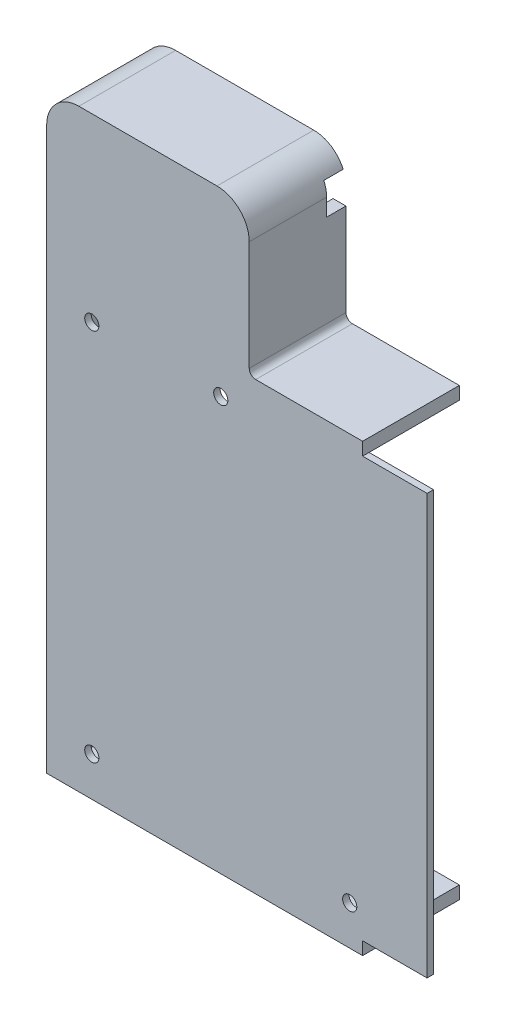
SolidWorks part; units mm, degrees
other "Markup1"
sketch "Sketch13" plane through (0.4487, 1125.5894, 1303.4729) normal (-0.633, 0.4523, -0.6282) x (-0.2198, -0.8831, -0.4145)
ref_plane "Front Plane" through (0, 0, 0) normal (0, 0, 1) x (1, 0, 0)
ref_plane "Top Plane" through (0, 0, 0) normal (0, 1, 0) x (1, 0, 0)
ref_plane "Right Plane" through (0, 0, 0) normal (1, 0, 0) x (0, 0, -1)
sketch "Sketch3" plane through (0, 0, 1303.4729) normal (0, 0, 1) x (1, 0, 0)
  line L0 (787.6501, 933.5894) -> (787.6501, 1120.5894) construction
  line L1 (787.6501, 1035.4965) -> (787.6501, 1120.5894)
  line L3 (818.0661, 1100.5894) -> (834.6501, 1100.5894) construction
  line L4 (815.0661, 1120.5894) -> (815.0661, 1103.5894) construction
  line L5 (790.6501, 1123.5894) -> (812.0661, 1123.5894) construction
  line L7 (818.0661, 1100.5894) -> (834.6501, 1100.5894)
  line L8 (815.0661, 1120.5894) -> (815.0661, 1103.5894)
  line L9 (790.6501, 1123.5894) -> (812.0661, 1123.5894)
  line L10 (787.6501, 1035.4965) -> (837.6501, 1035.4965) construction
  line L11 (787.6501, 1035.4965) -> (834.649, 1035.4965)
  line L13 (785.6501, 1033.4965) -> (834.649, 1033.4965)
  line L14 (785.6501, 1033.4965) -> (785.6501, 1120.5898)
  line L15 (790.6497, 1125.5894) -> (812.0665, 1125.5894)
  line L16 (817.0661, 1120.5898) -> (817.0661, 1103.5898)
  line L17 (818.0665, 1102.5894) -> (834.6505, 1102.5894)
  line L18 (834.6505, 1102.5894) -> (834.6501, 1100.5894)
  line L19 (834.649, 1035.4965) -> (834.649, 1033.4965)
  line L21 (839.6501, 1097.5898) -> (839.6501, 1033.4965) construction
  line L22 (837.6501, 1097.5894) -> (837.6501, 1035.4965) construction
  line L23 (787.6501, 1035.4965) -> (837.6501, 1035.4965) construction
  line L24 (785.6501, 1033.4965) -> (839.6501, 1033.4965) construction
  arc A1 (815.0661, 1103.5894) -> (818.0661, 1100.5894) centre (818.0672, 1103.5905) ccw construction
  arc A2 (815.0661, 1120.5894) -> (812.0661, 1123.5894) centre (812.065, 1120.5883) ccw construction
  arc A3 (790.6501, 1123.5894) -> (787.6501, 1120.5894) centre (790.6512, 1120.5883) ccw construction
  arc A5 (815.0661, 1103.5894) -> (818.0661, 1100.5894) centre (818.0672, 1103.5905) ccw
  arc A6 (815.0661, 1120.5894) -> (812.0661, 1123.5894) centre (812.065, 1120.5883) ccw
  arc A7 (790.6501, 1123.5894) -> (787.6501, 1120.5894) centre (790.6512, 1120.5883) ccw
  arc A8 (790.6497, 1125.5894) -> (785.6501, 1120.5898) centre (790.6512, 1120.5883) ccw
  arc A9 (817.0661, 1120.5898) -> (812.0665, 1125.5894) centre (812.065, 1120.5883) ccw
  arc A10 (817.0661, 1103.5898) -> (818.0665, 1102.5894) centre (818.0672, 1103.5905) ccw
  arc A12 (837.6501, 1097.5894) -> (834.6501, 1100.5894) centre (834.649, 1097.5883) ccw construction
  arc A13 (839.6501, 1097.5898) -> (834.6505, 1102.5894) centre (834.649, 1097.5883) ccw construction
  point P3 (0, 0)
  dimension "D1" = 2
sketch "Sketch6" plane through (0, 0, 1303.4729) normal (0, 0, 1) x (1, 0, 0)
  line L0 (787.6501, 1035.4965) -> (834.649, 1035.4965) construction
  line L2 (818.0661, 1100.5894) -> (834.6501, 1100.5894) construction
  line L3 (815.0661, 1120.5894) -> (815.0661, 1103.5894) construction
  line L4 (790.6501, 1123.5894) -> (812.0661, 1123.5894) construction
  line L5 (787.6501, 1035.4965) -> (787.6501, 1120.5894) construction
  line L6 (787.6501, 1035.4965) -> (834.649, 1035.4965)
  line L8 (818.0661, 1100.5894) -> (834.6501, 1100.5894)
  line L9 (815.0661, 1120.5894) -> (815.0661, 1103.5894)
  line L10 (790.6501, 1123.5894) -> (812.0661, 1123.5894)
  line L11 (787.6501, 1035.4965) -> (787.6501, 1120.5894)
  line L12 (844.6501, 1100.5894) -> (844.649, 1035.4965)
  line L13 (834.6501, 1100.5894) -> (844.6501, 1100.5894)
  line L14 (834.649, 1035.4965) -> (844.649, 1035.4965)
  arc A1 (815.0661, 1103.5894) -> (818.0661, 1100.5894) centre (818.0672, 1103.5905) ccw construction
  arc A2 (815.0661, 1120.5894) -> (812.0661, 1123.5894) centre (812.065, 1120.5883) ccw construction
  arc A3 (790.6501, 1123.5894) -> (787.6501, 1120.5894) centre (790.6512, 1120.5883) ccw construction
  arc A5 (815.0661, 1103.5894) -> (818.0661, 1100.5894) centre (818.0672, 1103.5905) ccw
  arc A6 (815.0661, 1120.5894) -> (812.0661, 1123.5894) centre (812.065, 1120.5883) ccw
  arc A7 (790.6501, 1123.5894) -> (787.6501, 1120.5894) centre (790.6512, 1120.5883) ccw
extrude "Boss-Extrude1" add sketch "Sketch3" along normal blind 15
extrude "Boss-Extrude2" add sketch "Sketch6" along normal blind 15
extrude "Cut-Extrude1" cut sketch "Sketch6<2>" along normal blind 14
sketch "Sketch6<2>" plane through (0, 0, 1303.4729) normal (0, 0, 1) x (1, 0, 0) same geometry as "Sketch6"
sketch "Sketch8" plane through (0, 0, 1303.4729) normal (0, 0, 1) x (1, 0, 0)
  line L10 (791.5267, 1122.6166) -> (784.8275, 1122.6166)
  line L11 (791.5267, 1122.6166) -> (791.5267, 1117.8952)
  line L12 (791.5267, 1117.8952) -> (784.8275, 1117.8952)
  line L13 (784.8275, 1122.6166) -> (784.8275, 1117.8952)
  line L14 (809.8444, 1122.6166) -> (818.0733, 1122.6166)
  line L15 (809.8444, 1122.6166) -> (809.8444, 1117.8952)
  line L16 (809.8444, 1117.8952) -> (818.0733, 1117.8952)
  line L17 (818.0733, 1122.6166) -> (818.0733, 1117.8952)
extrude "Cut-Extrude7" cut sketch "Sketch8" along normal blind 3
sketch "Sketch10" plane through (0, 0, 1303.4729) normal (0, 0, 1) x (1, 0, 0)
  circle A0 centre (832.6501, 1039.5894) radius 1.1 construction
  circle A1 centre (792.6501, 1039.5894) radius 1.1 construction
  circle A2 centre (792.6501, 1097.5894) radius 1.1 construction
  circle A3 centre (812.6501, 1097.5894) radius 1.1 construction
  circle A4 centre (832.6501, 1039.5894) radius 1.1
  circle A5 centre (792.6501, 1039.5894) radius 1.1
  circle A6 centre (792.6501, 1097.5894) radius 1.1
  circle A7 centre (812.6501, 1097.5894) radius 1.1
extrude "Cut-Extrude9" cut sketch "Sketch10" along normal up to surface (15 mm away) up to face at (819.5312, 1087.8581, 1318.4729)
sketch "Sketch14" plane through (0, 0, 0) normal (0, 0, 1) x (1, 0, 0)
  line L6 (854.6501, 1097.5898) -> (854.6501, 1033.4965)
  line L7 (849.649, 1033.4965) -> (854.6501, 1033.4965)
  line L8 (849.649, 1035.4965) -> (852.6501, 1035.4965)
  line L9 (852.6501, 1097.5894) -> (852.6501, 1035.4965)
  line L10 (849.6505, 1102.5894) -> (834.6505, 1102.5894)
  line L11 (834.6505, 1102.5894) -> (834.6501, 1100.5894)
  line L12 (834.6501, 1100.5894) -> (849.6501, 1100.5894)
  line L13 (849.649, 1035.4965) -> (834.6503, 1035.4965)
  line L14 (787.6501, 1035.4965) -> (834.649, 1035.4965) construction
  line L15 (834.6503, 1035.4965) -> (834.6503, 1033.4965)
  line L16 (785.6501, 1033.4965) -> (834.649, 1033.4965) construction
  line L17 (834.6503, 1033.4965) -> (849.649, 1033.4965)
  line L18 (818.0665, 1102.5894) -> (834.6505, 1102.5894) construction
  line L19 (787.6501, 1035.4965) -> (787.6501, 1120.5894) construction
  arc A2 (852.6501, 1097.5894) -> (849.6501, 1100.5894) centre (849.649, 1097.5883) ccw
  arc A3 (854.6501, 1097.5898) -> (849.6505, 1102.5894) centre (849.649, 1097.5883) ccw
